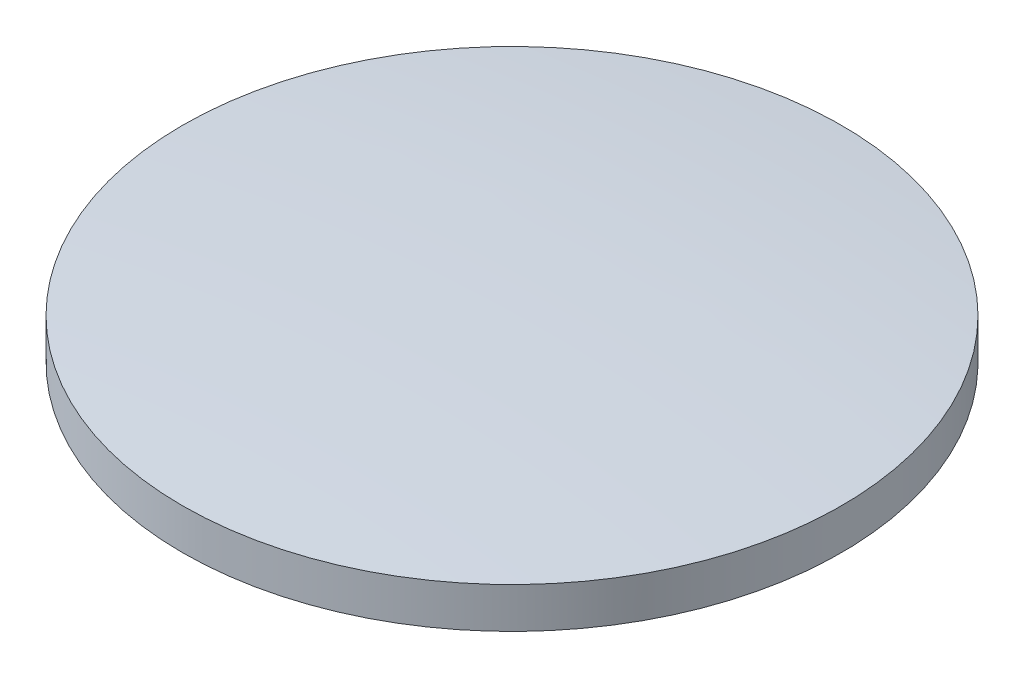
SolidWorks part; units mm, degrees
material "Acrylic (Medium-high impact)"
ref_plane "Front Plane" through (0, 0, 0) normal (0, 0, 1) x (1, 0, 0)
ref_plane "Top Plane" through (0, 0, 0) normal (0, 1, 0) x (1, 0, 0)
ref_plane "Right Plane" through (0, 0, 0) normal (1, 0, 0) x (0, 0, -1)
sketch "Sketch1" plane through (0, 0, 0) normal (0, 0, 1) x (1, 0, 0)
  line L0 (0, 0) -> (-25.95, 0)
  line L1 (-25.95, 0) -> (-25.95, 3.2)
  line L2 (-25.95, 3.2) -> (0, 3.2) construction
  line L3 (0, 3.2) -> (0, 0)
  line L4 (0, 3.2) -> (0, 4.4)
  line L5 (0, 4.4) -> (-6.7786, 4.4) construction
  arc A0 (0, 4.4) -> (-25.95, 3.2) centre (0, -276.7844) ccw
  point P8 (-6.7786, 5.5293)
  dimension "D1" = 25.95
  dimension "D2" = 4.4
  dimension "D3" = 1.2
revolve "Revolve1" add sketch "Sketch1" angle 360 about L3
ref_axis "Axis1" through (0, 0, 0) along (0, 1, 0)
